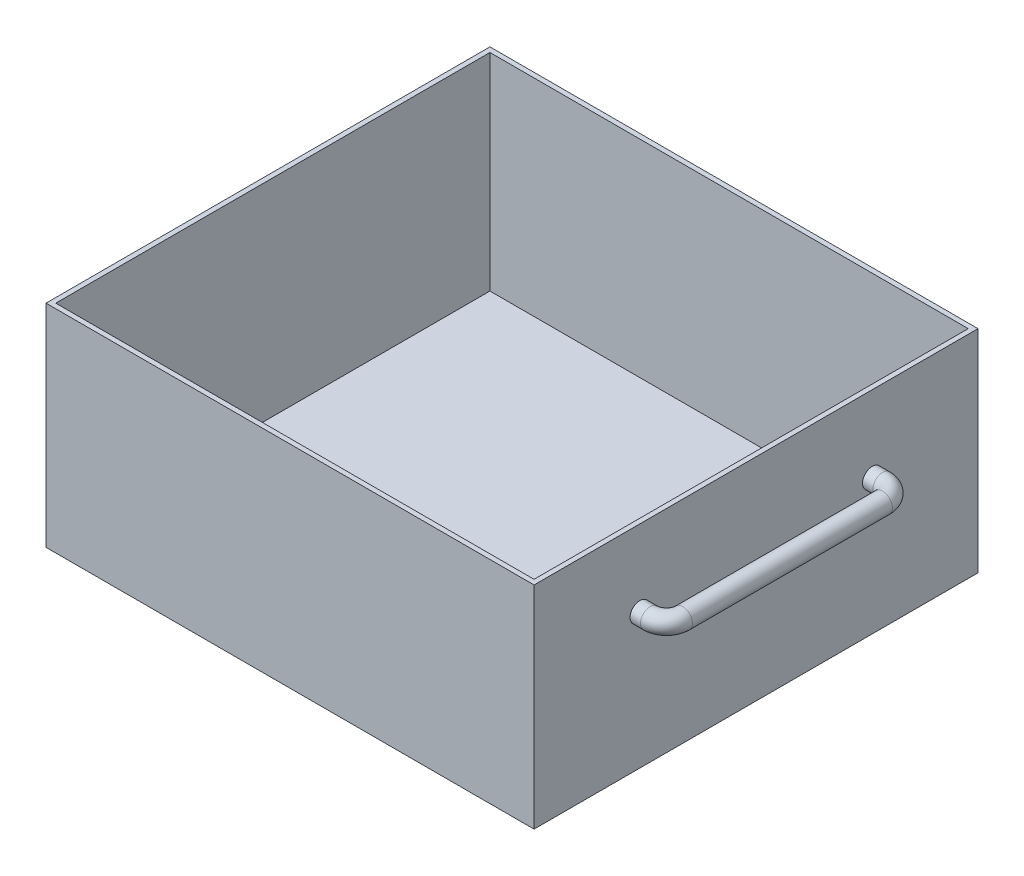
SolidWorks part; units mm, degrees
ref_plane "前视" through (0, 0, 0) normal (0, 0, 1) x (1, 0, 0)
ref_plane "上视" through (0, 0, 0) normal (0, 1, 0) x (1, 0, 0)
ref_plane "右视" through (0, 0, 0) normal (1, 0, 0) x (0, 0, -1)
sketch "Sketch1" plane through (0, 0, 0) normal (0, 1, 0) x (1, 0, 0)
  line L1 (-136.8201, 119.8745) -> (163.1799, 119.8745)
  line L2 (-136.8201, 119.8745) -> (-136.8201, -153.0005)
  line L3 (-136.8201, -153.0005) -> (163.1799, -153.0005)
  line L4 (163.1799, 119.8745) -> (163.1799, -153.0005)
  dimension "D1" = 300
  dimension "D2" = 272.875
extrude "Boss-Extrude1" add sketch "Sketch1" along normal blind 130
shell "Shell1" thickness 3 removed face at (13.1799, 130, 16.563)
sketch "Sketch2" plane through (163.1799, 0, 0) normal (1, 0, 0) x (0, 0, -1)
  line L1 (-153.0005, 130) -> (-153.0005, 0) construction
  circle A0 centre (-88.0005, 83.1724) radius 6
  point P9 (54.8745, 83.1724)
  dimension "D2" = 65
ref_plane "Plane1" through (0, 83.1724, 0) normal (0, 1, 0) x (1, 0, 0)
sketch "Sketch4" plane through (0, 83.1724, 0) normal (0, 1, 0) x (1, 0, 0)
  line L0 (163.1799, -88.0005) -> (169.5656, -88.0005)
  line L1 (179.5656, -78.0005) -> (179.5656, 44.8745)
  line L2 (169.5656, 54.8745) -> (163.1799, 54.8745)
  arc A0 (179.5656, -78.0005) -> (169.5656, -88.0005) centre (169.5656, -78.0005) cw
  arc A1 (179.5656, 44.8745) -> (169.5656, 54.8745) centre (169.5656, 44.8745) ccw
  dimension "D1" = 10
sweep "Sweep2" add profiles "Sketch2" path "Sketch4"
